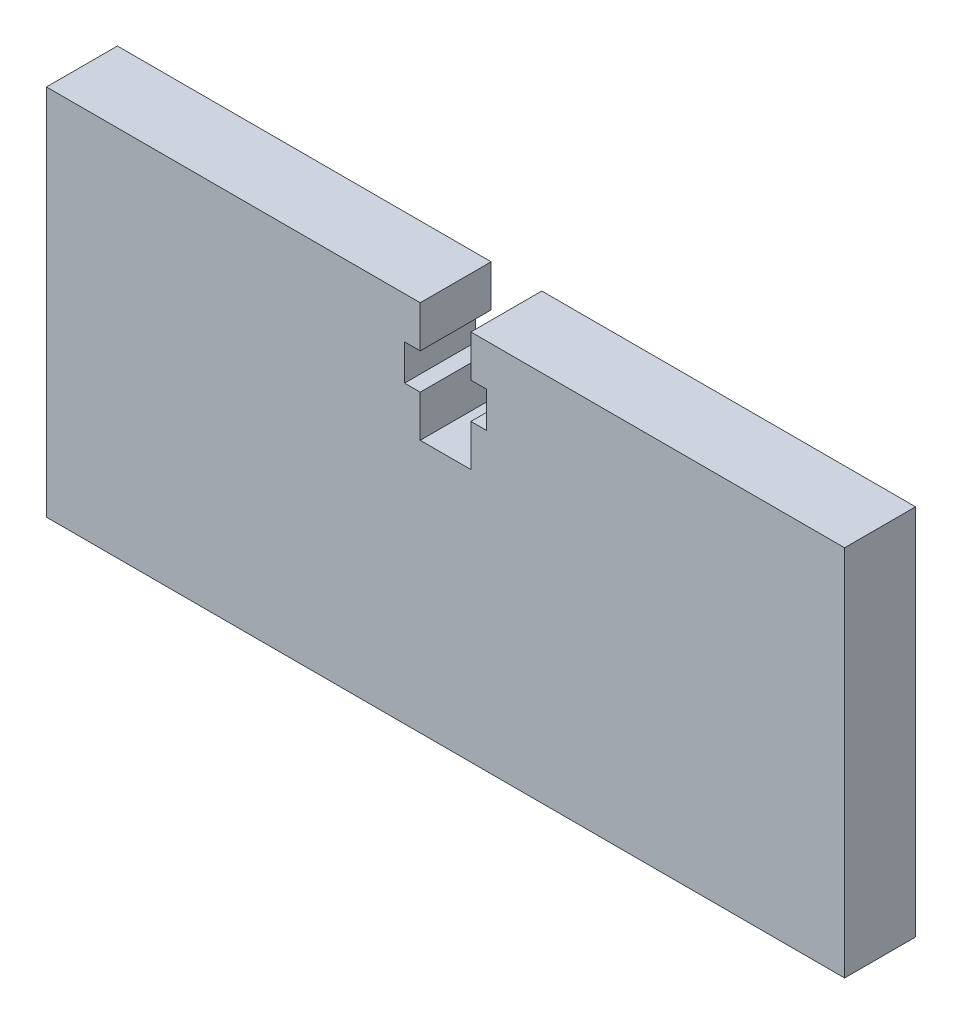
SolidWorks part; units mm, degrees
ref_plane "Front Plane" through (0, 0, 0) normal (0, 0, 1) x (1, 0, 0)
ref_plane "Top Plane" through (0, 0, 0) normal (0, 1, 0) x (1, 0, 0)
ref_plane "Right Plane" through (0, 0, 0) normal (1, 0, 0) x (0, 0, -1)
sketch "Sketch1" plane through (0, 0, 0) normal (0, 0, 1) x (1, 0, 0)
  line L0 (0, 16.51) -> (0, -7.29) construction
  line L2 (-26.797, -8.51) -> (-26.797, 16.51)
  line L3 (-26.797, 16.51) -> (-1.7, 16.51)
  line L4 (26.797, -8.51) -> (26.797, 16.51)
  line L5 (-26.797, -16.51) -> (26.797, 16.51) construction
  line L6 (-26.797, 16.51) -> (26.797, -16.51) construction
  line L7 (-13.4509, -7.29) -> (13.4509, -7.29) construction
  line L8 (0, 5.91) -> (26.797, 5.91) construction
  line L9 (-1.7, 16.51) -> (-1.7, 13.71)
  line L10 (-1.7, 13.71) -> (-2.75, 13.71)
  line L11 (-2.75, 13.71) -> (-2.75, 11.31)
  line L12 (-2.75, 11.31) -> (-1.7, 11.31)
  line L13 (-1.7, 11.31) -> (-1.7, 8.51)
  line L14 (-1.7, 8.51) -> (1.7, 8.51)
  line L15 (-2.75, 12.51) -> (0, 12.51) construction
  line L16 (1.7, 11.31) -> (1.7, 8.51)
  line L17 (2.75, 11.31) -> (1.7, 11.31)
  line L18 (2.75, 13.71) -> (2.75, 11.31)
  line L19 (1.7, 13.71) -> (2.75, 13.71)
  line L20 (1.7, 16.51) -> (1.7, 13.71)
  line L21 (1.7, 16.51) -> (26.797, 16.51)
  line L22 (0, 0) -> (26.797, 0) construction
  line L34 (-26.797, -8.51) -> (26.797, -8.51)
  point P0 (0, 0)
  point P23 (0, 8.51)
  dimension "D1" = 33.02
  dimension "D2" = 53.594
  dimension "D3" = 1.7
  dimension "D4" = 2.75
  dimension "D5" = 8
  dimension "D6" = 4
  dimension "D7" = 2.4
extrude "Boss-Extrude1" add sketch "Sketch1" along normal blind 4.7625 contours L4 L21 L20 L19 L18 L17 L16 L14 L13 L12 L11 L10 L9 L3 L2 region at (0, 3.7904, 0)
equation "\"D6@Sketch1\"=\"D5@Sketch1\"/2"
